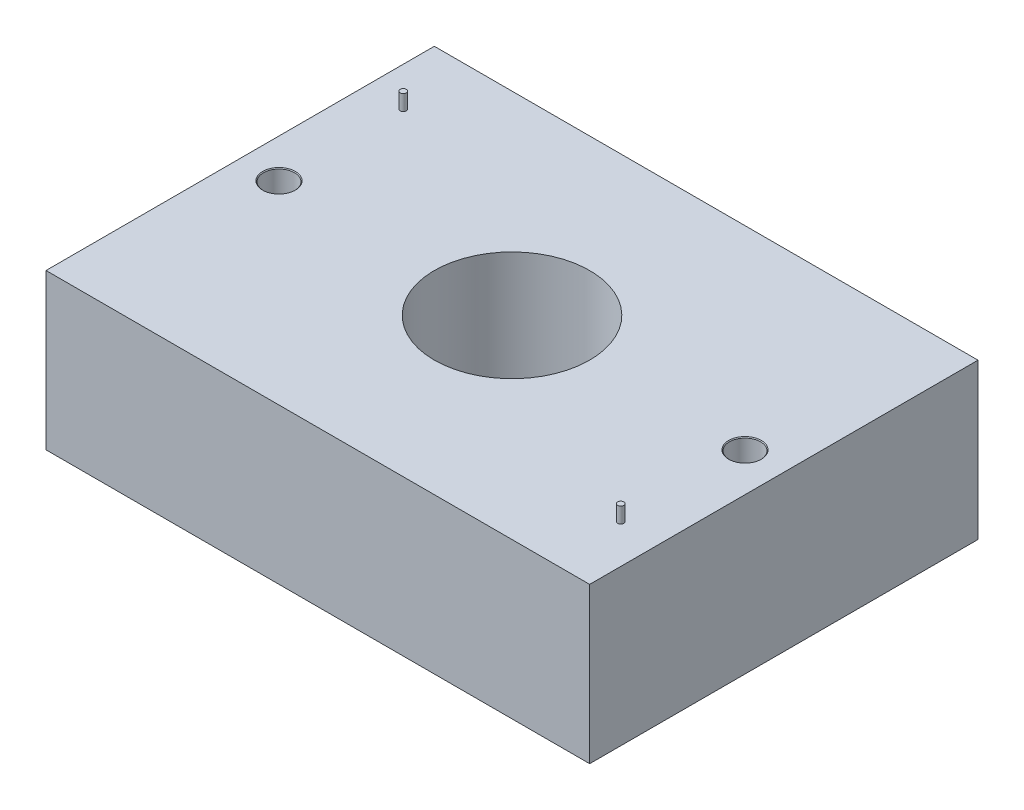
SolidWorks part; units mm, degrees
note: The reader was unsure of these and kept them because the rebuilt part matched: shared geometry of "Sketch1<4>".
ref_plane "Front Plane" through (0, 0, 0) normal (0, 0, 1) x (1, 0, 0)
ref_plane "Top Plane" through (0, 0, 0) normal (0, 1, 0) x (1, 0, 0)
ref_plane "Right Plane" through (0, 0, 0) normal (1, 0, 0) x (0, 0, -1)
sketch "Sketch1" plane through (0, 0, 0) normal (0, 1, 0) x (1, 0, 0)
  line L1 (0, 0) -> (175, 0)
  line L2 (0, 0) -> (0, 125)
  line L3 (0, 125) -> (175, 125)
  line L4 (175, 0) -> (175, 125)
  circle A0 centre (87.5, 62.5) radius 25
  circle A1 centre (162.5, 22.5) radius 1
  circle A2 centre (12.5, 102.5) radius 1
  point P7 (12.5, 62.5)
  point P8 (162.5, 62.5)
  point P13 (0, 0)
  point P14 (0, 62.5)
  point P15 (0, 0)
  point P16 (0, 0)
  point P17 (0, 0)
  dimension "D6" = 2
  dimension "D7" = 2
  dimension "D8" = 50
  dimension "D1" = 175
  dimension "D2" = 125
  dimension "D3" = 22.5
  dimension "D4" = 62.5
  dimension "D5" = 80
  dimension "D9" = 12.5
  dimension "D10" = 150
  dimension "D11" = 87.5
extrude "Boss-Extrude1" add sketch "Sketch1" against normal blind 50 contours A0 | L2 L3 L4 L1
extrude "Boss-Extrude2" add sketch "Sketch1<4>" along normal blind 5 contours A2 | A1
sketch "Sketch1<4>" plane through (0, 0, 0) normal (0, 1, 0) x (1, 0, 0) same geometry as "Sketch1"
hole_wizard "CBORE for M12 Hex Head Machine Screw1" positions "3DSketch1" profile "Sketch5" counterbore size "M12" standard "ANSI Metric"
sketch3d "3DSketch1"
  line L2 (0, 0, 0) -> (0, 0, -125) construction
  line L3 (0, 0, -125) -> (175, 0, -125) construction
  point P0 (12.5, 0, -62.5)
  point P2 (162.5, 0, -62.5)
  point P5 (0, 0, 0)
  point P6 (166.2974, 0, -62.4986)
  point P7 (155.9155, 0, -62.4986)
  point P8 (162.0547, 0, -62.4986)
  point P9 (156.4606, 0, -64.207)
  point P10 (162.4891, 0, -62.4986)
  point P11 (0, 0, 0)
  point P23 (0, 0, 0)
  point P24 (0, 0, 0)
  point P25 (0, 0, 0)
  point P26 (0, 0, 0)
  dimension "D1" = 150
  dimension "D2" = 12.5
  dimension "D3" = 62.5
sketch "Sketch5" plane through (12.5, 0, -62.5) normal (1, 0, 0) x (0, 0, 1)
  line L0 (0, 0) -> (0, 28)
  line L1 (0, 28) -> (4.25, 25.4463)
  line L2 (4.25, 25.4463) -> (4.25, 20)
  line L3 (4.25, 20) -> (5, 20)
  line L5 (5, 20) -> (5, 0.25)
  line L6 (5, 0.25) -> (5.25, 0)
  line L7 (5.25, 0) -> (0, 0)
  line L8 (-5, 0.25) -> (-5.25, 0) construction
  line L10 (0, 28) -> (-4.25, 25.4463) construction
  line L11 (0, -6.35) -> (0, 107.95) construction
  dimension "Hole Dia." = 8.5
  dimension "Hole Depth" = 28
  dimension "C'Bore Dia." = 10
  dimension "C'Bore Depth" = 20
  dimension "Near C'Sink Dia." = 10.5
  dimension "Near C'Sink Angle" = 90
  dimension "Drill Angle" = 118
thread "Thread1" [suppressed] pitch 1 start angle 0, offset 0, length 0, pitch 1, diameter 10
ref_plane "Plane1" through (7.5, -0.25, -62.5) normal (0, 0, 1) x (-1, 0, 0)
sketch "Thread Profile1" plane through (7.5, -0.25, -62.5) normal (0, 0, 1) x (-1, 0, 0)
  line L0 (0, 0) -> (0, 1) construction
  line L11 (0, 0) -> (0, 0.875)
  line L12 (0, 0.875) -> (-0.5413, 0.5625)
  line L13 (-0.5413, 0.5625) -> (-0.5413, 0.3125)
  line L15 (-0.5413, 0.3125) -> (0, 0)
  line L17 (-0.5413, 0.4375) -> (0, 0.4375) construction
  point P2 (0, 0)
  dimension "Pitch" = 1
  dimension "Profile_Angle" = 60
  dimension "Profile_Land" = 0.25
  dimension "Profile_Height" = 0.5413
thread "Thread2" [suppressed] pitch 1 start angle 0, offset 0, length 0, pitch 1, diameter 10
ref_plane "Plane2" through (157.5, -0.25, -62.5) normal (0, 0, 1) x (-1, 0, 0)
sketch "Thread Profile2" plane through (157.5, -0.25, -62.5) normal (0, 0, 1) x (-1, 0, 0)
  line L0 (0, 0) -> (0, 1) construction
  line L11 (0, 0) -> (0, 0.875)
  line L12 (0, 0.875) -> (-0.5413, 0.5625)
  line L13 (-0.5413, 0.5625) -> (-0.5413, 0.3125)
  line L15 (-0.5413, 0.3125) -> (0, 0)
  line L17 (-0.5413, 0.4375) -> (0, 0.4375) construction
  point P2 (0, 0)
  dimension "Pitch" = 1
  dimension "Profile_Angle" = 60
  dimension "Profile_Land" = 0.25
  dimension "Profile_Height" = 0.5413
